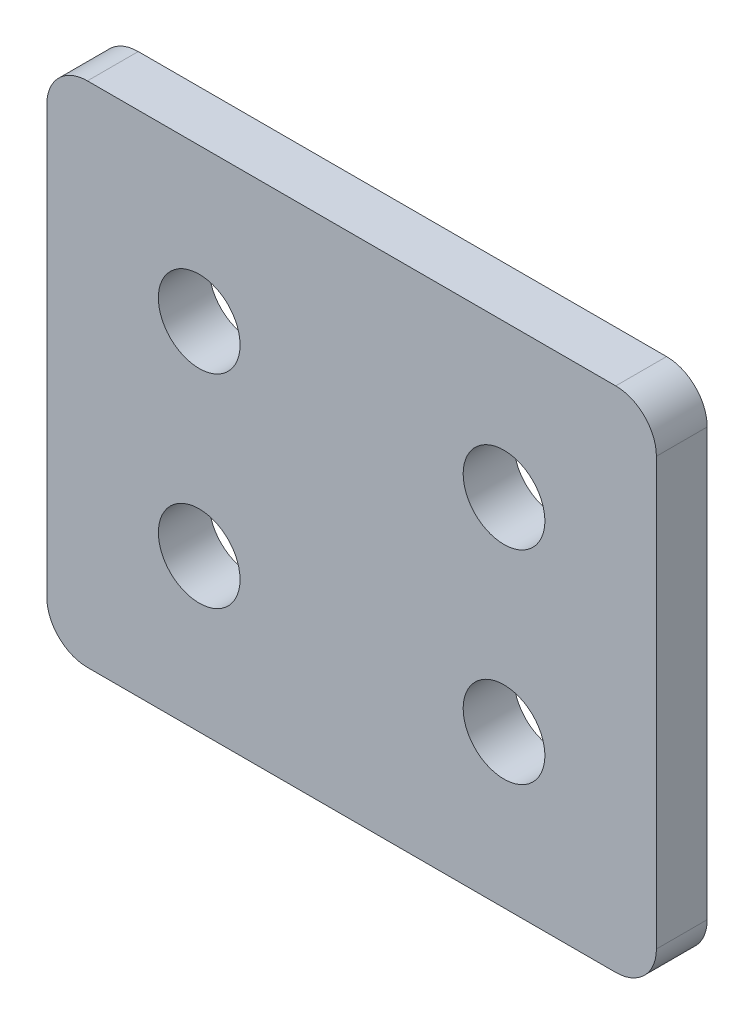
SolidWorks part; units mm, degrees
material "6061-T6 (SS)"
ref_plane "Front Plane" through (0, 0, 0) normal (0, 0, 1) x (1, 0, 0)
ref_plane "Top Plane" through (0, 0, 0) normal (0, 1, 0) x (1, 0, 0)
ref_plane "Right Plane" through (0, 0, 0) normal (1, 0, 0) x (0, 0, -1)
sketch "Sketch1" plane through (0, 0, 0) normal (0, 0, 1) x (1, 0, 0)
  line L0 (-9.525, -6.35) -> (-9.525, 6.35) construction
  line L5 (-19.05, -15.875) -> (19.05, -15.875)
  line L6 (-19.05, -15.875) -> (-19.05, 15.875)
  line L11 (-19.05, 15.875) -> (19.05, 15.875)
  line L15 (19.05, -15.875) -> (19.05, 15.875)
  line L16 (-19.05, -15.875) -> (19.05, 15.875) construction
  line L17 (-19.05, 15.875) -> (19.05, -15.875) construction
  line L18 (0, 15.875) -> (0, -15.875) construction
  circle A13 centre (-9.525, -6.35) radius 2.5527
  circle A14 centre (-9.525, 6.35) radius 2.5527
  circle A17 centre (9.525, -6.35) radius 2.5527
  circle A18 centre (9.525, 6.35) radius 2.5527
  point P0 (0, 0)
  point P13 (-9.525, 0)
  dimension "D2" = 12.7
  dimension "D4" = 19.05
  dimension "D5" = 5.1054
  dimension "D7" = 31.75
  dimension "D1" = 2
  dimension "D6" = 38.1
extrude "Boss-Extrude1" add sketch "Sketch1" along normal blind 3.175
fillet "Fillet1" radius 2.54 4 edges at (-19.05, 15.875, 1.5875) (-19.05, -15.875, 1.5875) (19.05, -15.875, 1.5875) (19.05, 15.875, 1.5875)
